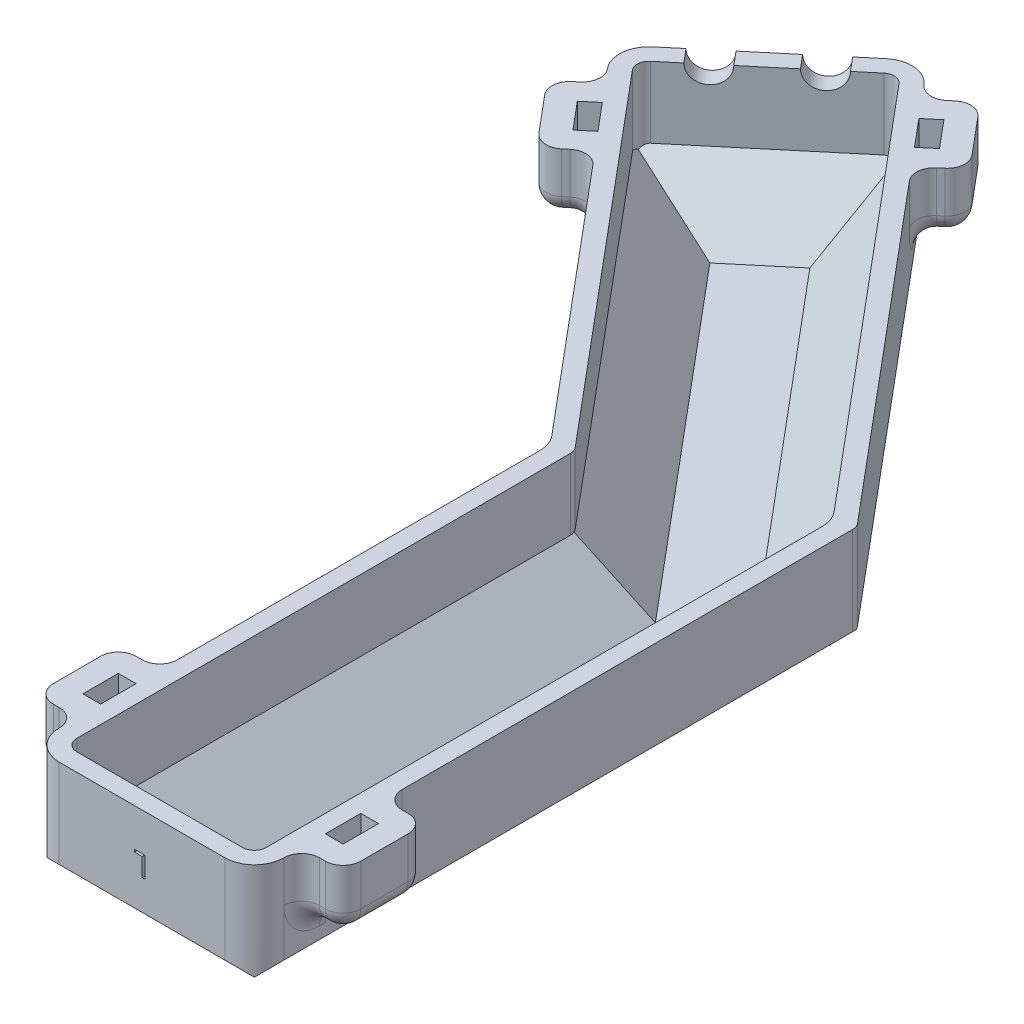
SolidWorks part; units mm, degrees
ref_plane "Front Plane" through (0, 0, 0) normal (0, 0, 1) x (1, 0, 0)
ref_plane "Top Plane" through (0, 0, 0) normal (0, 1, 0) x (1, 0, 0)
ref_plane "Right Plane" through (0, 0, 0) normal (1, 0, 0) x (0, 0, -1)
sketch "Sketch1" plane through (0, 0, 0) normal (0, 1, 0) x (1, 0, 0)
  line L0 (0, -95) -> (0, 0) construction
  line L1 (0, 0) -> (-57.8509, 68.944) construction
  line L2 (19, -95) -> (19, 6.9154)
  line L3 (-19, -95) -> (-19, -6.9154)
  line L4 (-19, -95) -> (19, -95)
  line L5 (19, 6.9154) -> (-43.296, 81.157)
  line L6 (-72.4057, 56.731) -> (-43.296, 81.157)
  line L7 (-72.4057, 56.731) -> (-19, -6.9154)
  line L8 (-68.1792, 56.3613) -> (-43.6658, 76.9305) construction
  line L9 (-68.1792, 56.3613) -> (-16, -5.8235) construction
  line L10 (-16, -5.8235) -> (-16, -92) construction
  line L11 (-16, -92) -> (16, -92) construction
  line L12 (16, -92) -> (16, 5.8235) construction
  line L13 (16, 5.8235) -> (-43.6658, 76.9305) construction
  point P9 (0, -95)
  point P10 (-57.8509, 68.944)
  point P12 (-55.9225, 66.6459)
  point P13 (0, -92)
  dimension "D1" = 95
  dimension "D2" = 90
  dimension "D3" = 38
  dimension "D4" = 38
  dimension "D5" = 140
  dimension "D6" = 32
  dimension "D7" = 32
  dimension "D8" = 3
  dimension "D9" = 3
extrude "Boss-Extrude1" add sketch "Sketch1" along normal blind 25
sketch "Sketch2" plane through (0, 25, 0) normal (0, 1, 0) x (1, 0, 0)
  line L0 (-68.1792, 56.3613) -> (-43.6658, 76.9305)
  line L1 (-68.1792, 56.3613) -> (-16, -5.8235)
  line L2 (-16, -5.8235) -> (-16, -92)
  line L3 (-16, -92) -> (16, -92)
  line L4 (16, -92) -> (16, 5.8235)
  line L5 (16, 5.8235) -> (-43.6658, 76.9305)
  line L6 (0, 0) -> (-57.8509, 68.944) construction
  line L7 (-43.296, 81.157) -> (-72.4057, 56.731) construction
  line L8 (0, 0) -> (0, -95) construction
  line L9 (-19, -95) -> (19, -95) construction
  point P0 (-55.9225, 66.6459)
  point P1 (0, -92)
  dimension "D1" = 32
  dimension "D2" = 32
  dimension "D3" = 3
  dimension "D4" = 3
extrude "Cut-Extrude1" cut sketch "Sketch2" against normal blind 22
chamfer "Chamfer1" distance 10 angle 45 12 edges at (-55.9225, 3, -66.6459) (-13.8329, 3, -41.377) (16, 3, 43.0882) (0, 3, 92) (-16, 3, 48.9118) (-42.0896, 3, -25.2689) (-45.7029, 0, -24.9078) (-57.8509, 0, -68.944) (-12.148, 0, -44.0362) (19, 0, 44.0423) (-19, 0, 50.9577) (0, 0, 95)
fillet "Fillet1" radius 2 6 edges at (-16, 19, 92) (16, 19, 92) (-16, 19, 5.8235) (19, 17.5, -6.9154) (-68.1792, 19, -56.3613) (-43.6658, 19, -76.9305)
fillet "Fillet2" radius 5 6 edges at (-19, 17.5, 95) (19, 17.5, 95) (-19, 17.5, 6.9154) (16, 19, -5.8235) (-43.296, 17.5, -81.157) (-72.4057, 17.5, -56.731)
sketch "Sketch3" plane through (-14.5548, 0, 12.213) normal (-0.766, 0, 0.6428) x (0.6428, 0, 0.766)
  line L0 (-85, 25) -> (-8.7353, 25) construction
  line L1 (-68, 15) -> (-82, 15)
  line L2 (-68, 15) -> (-68, 25)
  line L3 (-68, 25) -> (-82, 25)
  line L4 (-82, 15) -> (-82, 25)
  line L5 (-68, 15) -> (-82, 25) construction
  line L6 (-68, 25) -> (-82, 15) construction
  line L7 (-85, 25) -> (-85, 10) construction
  point P0 (-75, 20)
  dimension "D1" = 10
  dimension "D2" = 14
  dimension "D3" = 3
sketch "Sketch4" plane through (14.5548, 0, -12.213) normal (0.766, 0, -0.6428) x (-0.6428, 0, -0.766)
  line L0 (-6.1875, 25) -> (85, 25) construction
  line L1 (82, 15) -> (68, 15)
  line L2 (82, 15) -> (82, 25)
  line L3 (82, 25) -> (68, 25)
  line L4 (68, 15) -> (68, 25)
  line L5 (82, 15) -> (68, 25) construction
  line L6 (82, 25) -> (68, 15) construction
  line L7 (85, 10) -> (85, 25) construction
  point P0 (75, 20)
  dimension "D1" = 3
  dimension "D2" = 10
  dimension "D3" = 14
sketch "Sketch6" plane through (-19, 0, 0) normal (-1, 0, 0) x (0, 0, 1)
  line L0 (8.7353, 25) -> (90, 25) construction
  line L1 (87, 15) -> (73, 15)
  line L2 (87, 15) -> (87, 25)
  line L3 (87, 25) -> (73, 25)
  line L4 (73, 15) -> (73, 25)
  line L5 (87, 15) -> (73, 25) construction
  line L6 (87, 25) -> (73, 15) construction
  line L7 (90, 10) -> (90, 25) construction
  point P0 (80, 20)
  dimension "D1" = 3
  dimension "D2" = 14
  dimension "D3" = 10
sketch "Sketch7" plane through (19, 0, 0) normal (1, 0, 0) x (0, 0, -1)
  line L0 (-90, 25) -> (6.1875, 25) construction
  line L1 (-73, 15) -> (-87, 15)
  line L2 (-73, 15) -> (-73, 25)
  line L3 (-73, 25) -> (-87, 25)
  line L4 (-87, 15) -> (-87, 25)
  line L5 (-73, 15) -> (-87, 25) construction
  line L6 (-73, 25) -> (-87, 15) construction
  line L7 (-90, 25) -> (-90, 10) construction
  point P0 (-80, 20)
  dimension "D1" = 10
  dimension "D2" = 14
  dimension "D3" = 3
sketch "Sketch9" plane through (0, 0, 95) normal (0, 0, 1) x (1, 0, 0)
  line L0 (0, 10) -> (0, 25) construction
  line L1 (-14, 10) -> (14, 10) construction
  line L2 (-14, 25) -> (14, 25) construction
  line L3 (14, 17.5) -> (-14, 17.5) construction
  line L4 (14, 10) -> (14, 25) construction
  line L5 (-14, 25) -> (-14, 10) construction
  text T0 "<b><r180>L</r></b>"
extrude "Cut-Extrude4" cut sketch "Sketch9" against normal blind 0.5
extrude "Boss-Extrude2" add sketch "Sketch3" along normal blind 7
extrude "Boss-Extrude3" add sketch "Sketch4" along normal blind 7
extrude "Boss-Extrude4" add sketch "Sketch6" along normal blind 7
extrude "Boss-Extrude5" add sketch "Sketch7" along normal blind 7
sketch "Sketch10" plane through (0, 25, 0) normal (0, 1, 0) x (1, 0, 0)
  line L0 (-66.9904, 45.6101) -> (-64.6923, 47.5385)
  line L1 (-66.9904, 45.6101) -> (-63.1337, 41.0139)
  line L2 (-64.6923, 47.5385) -> (-60.8356, 42.9422)
  line L3 (-63.1337, 41.0139) -> (-60.8356, 42.9422)
  line L4 (-35.5826, 71.9644) -> (-33.2845, 73.8928)
  line L5 (-35.5826, 71.9644) -> (-31.7259, 67.3682)
  line L6 (-33.2845, 73.8928) -> (-29.4277, 69.2965)
  line L7 (-31.7259, 67.3682) -> (-29.4277, 69.2965)
  line L8 (-58.2644, 39.8781) -> (-20.1698, -5.5213) construction
  line L9 (-72.6257, 46.1032) -> (-67.2634, 50.6027) construction
  line L10 (-32.7914, 79.5281) -> (-38.1537, 75.0286) construction
  line L11 (18.5321, 7.4731) -> (-29.1547, 64.304) construction
  line L12 (-22, -77) -> (-19, -77)
  line L13 (-22, -77) -> (-22, -83)
  line L14 (-19, -77) -> (-19, -83)
  line L15 (-22, -83) -> (-19, -83)
  line L16 (19, -77) -> (22, -77)
  line L17 (19, -77) -> (19, -83)
  line L18 (22, -77) -> (22, -83)
  line L19 (19, -83) -> (22, -83)
  line L20 (26, -73) -> (19, -73) construction
  line L21 (19, -73) -> (19, 6.1875) construction
  line L22 (-19, -8.7353) -> (-19, -73) construction
  line L23 (-26, -73) -> (-19, -73) construction
  dimension "D1" = 4
  dimension "D2" = 4
  dimension "D3" = 4
  dimension "D4" = 4
  dimension "D5" = 6
  dimension "D6" = 3
extrude "Cut-Extrude5" cut sketch "Sketch10" against normal through all
fillet "Fillet3" radius 3 36 edges at (-58.2644, 20, -39.8781) (-65.9779, 15, -49.0706) (19, 20, 87) (19, 15, 75) (-19, 20, 87) (-19, 20, 73) (-29.1547, 20, -64.304) (-38.1537, 20, -75.0286) (-60.9456, 15, -37.6283) (-59.55, 15, -41.4101) (-63.6267, 20, -35.3785) (-67.2634, 20, -50.6027) (-72.6257, 20, -46.1032) (-68.1262, 15, -40.7409) (-69.9446, 15, -48.3529) (26, 20, 87) (22.5, 15, 87) (19, 15, 85) (26, 15, 80) (19, 20, 73) (22.5, 15, 73) (26, 20, 73) (-26, 20, 87) (-22.5, 15, 87) (-19, 15, 85) (-19, 15, 75) (-26, 15, 80) (-26, 20, 73) (-22.5, 15, 73) (-30.4403, 15, -65.8361) (-26.4736, 15, -66.5537) (-23.7924, 20, -68.8035) (-35.4726, 15, -77.2784) (-28.2919, 15, -74.1658) (-36.8682, 15, -73.4965) (-32.7914, 20, -79.5281)
sketch "Sketch11" plane through (-57.8509, 0, -68.944) normal (-0.6428, 0, -0.766) x (-0.766, 0, 0.6428)
  line L0 (-14, 25) -> (14, 25) construction
  line L1 (0, 25) -> (0, 27.0321) construction
  circle A0 centre (7, 25) radius 3
  circle A1 centre (-7, 25) radius 3
  dimension "D1" = 6
  dimension "D2" = 7
extrude "Cut-Extrude6" cut sketch "Sketch11" against normal blind 10
